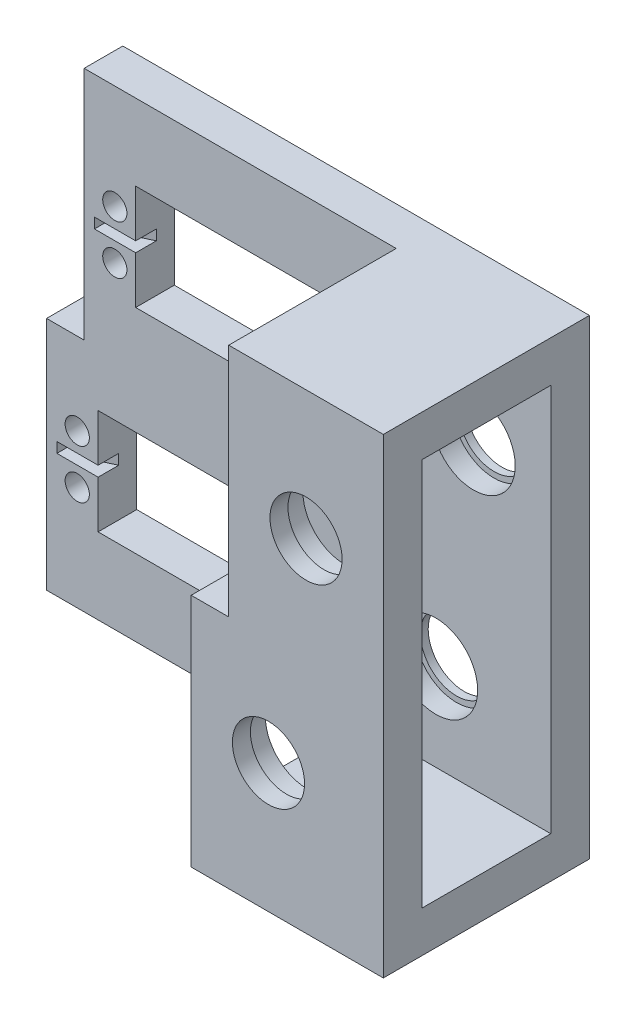
SolidWorks part; units mm, degrees
note: '?' marks a value the reader was unsure of.
ref_plane "Front Plane" through (0, 0, 0) normal (0, 0, 1) x (1, 0, 0)
ref_plane "Top Plane" through (0, 0, 0) normal (0, 1, 0) x (1, 0, 0)
ref_plane "Right Plane" through (0, 0, 0) normal (1, 0, 0) x (0, 0, -1)
sketch "Sketch1" plane through (0, 0, 0) normal (0, 0, 1) x (1, 0, 0)
  line L0 (-15, 0) -> (22.2932, 0)
  line L5 (-15, 91.3619) -> (22.2932, 91.3619)
  line L6 (-15, 0) -> (-15, 91.3619)
  line L7 (22.2932, 0) -> (22.2932, 91.3619)
  line L8 (0, 25) -> (7.2932, 66.3619) construction
  line L9 (0, 25) -> (0, 79.2) construction
  circle A1 centre (0, 25) radius 8.1
  circle A2 centre (7.2932, 66.3619) radius 8.1
  point P4 (0, 0)
  dimension "D2" = 16.2
  dimension "D5" = 25
  dimension "D4" = 15
  dimension "D6" = 25
  dimension "D8" = 42
  dimension "D9" = 10
  dimension "D10" = 15
extrude "Boss-Extrude1" add sketch "Sketch1" along normal blind 40
ref_plane "INNER WALL" through (0, 0, 39) normal (0, 0, 1) x (1, 0, 0)
ref_plane "OUTER WALL" through (0, 0, 32.65) normal (0, 0, 1) x (1, 0, 0)
sketch "Sketch2" plane through (0, 0, 0) normal (0, 1, 0) x (1, 0, 0)
  line L1 (-15, -7.5) -> (22.2932, -7.5)
  line L2 (-15, -7.5) -> (-15, -32.5)
  line L3 (-15, -32.5) -> (22.2932, -32.5)
  line L4 (22.2932, -7.5) -> (22.2932, -32.5)
  line L6 (-15, -40) -> (-15, 0) construction
  line L7 (22.2932, -40) -> (22.2932, 0) construction
  point P9 (22.2932, -20)
  point P10 (22.2932, -20)
  dimension "D1" = 25
extrude "Cut-Extrude1" cut sketch "Sketch2" along normal through all from offset 8
sketch "Sketch10" plane through (0, 0, 40) normal (0, 0, 1) x (1, 0, 0)
  circle A0 centre (7.2932, 66.3619) radius 8.1
  circle A1 centre (0, 25) radius 10.837
  circle A2 centre (7.2932, 66.3619) radius 7
  circle A3 centre (0, 25) radius 7
  circle A4 centre (7.2932, 66.3619) radius 8.1 construction
  circle A5 centre (0, 25) radius 8.1 construction
  dimension "D2" = 14
  dimension "D4" = 14
extrude "Boss-Extrude2" add sketch "Sketch10" against normal offset from surface (3.5 mm away) 4 up to face at (-8.1, 25, 32.5)
sketch "Sketch11" plane through (0, 0, 0) normal (0, 0, -1) x (-1, 0, 0)
  circle A0 centre (-7.2932, 66.3619) radius 8.1
  circle A1 centre (-7.2932, 66.3619) radius 7
  circle A2 centre (0, 25) radius 8.1
  circle A3 centre (0, 25) radius 7
  circle A4 centre (0, 25) radius 8.1 construction
  circle A5 centre (-7.2932, 66.3619) radius 8.1 construction
  dimension "D1" = 14
  dimension "D2" = 14
extrude "Boss-Extrude3" add sketch "Sketch11" against normal offset from surface (3.5 mm away) 4 up to face at (8.1, 25, 7.5)
ref_axis "Axis1" through (0, 25, 3.5) along (0, 0, -1)?
ref_plane "Plane1" through (0, 25, 0) normal (0, -1, 0) x (-1, 0, 0)
ref_axis "Axis2" through (7.2932, 66.3619, 3.5) along (0, 0, -1)?
ref_plane "Plane2" through (0, 66.3619, 0) normal (0, -1, 0) x (-1, 0, 0)
sketch "Sketch12" plane through (0, 0, 0) normal (0, 0, -1) x (-1, 0, 0)
  line L0 (-20.5113, 25) -> (20.5113, 25) construction
  line L1 (15, 0) -> (75.56, 0)
  line L2 (15, 0) -> (15, 91.3619)
  line L3 (15, 91.3619) -> (68.2668, 91.3619)
  line L5 (-20.5113, 66.3619) -> (20.5113, 66.3619) construction
  line L6 (24.66, 35.2) -> (65.56, 35.2)
  line L7 (24.66, 35.2) -> (24.66, 14.8)
  line L8 (24.66, 14.8) -> (65.56, 14.8)
  line L9 (65.56, 35.2) -> (65.56, 14.8)
  line L10 (-22.2932, 91.3619) -> (15, 91.3619) construction
  line L11 (17.3668, 76.5619) -> (58.2668, 76.5619)
  line L12 (17.3668, 76.5619) -> (17.3668, 56.1619)
  line L13 (17.3668, 56.1619) -> (58.2668, 56.1619)
  line L14 (58.2668, 76.5619) -> (58.2668, 56.1619)
  line L16 (15, 0) -> (-22.2932, 0) construction
  line L17 (15, 91.3619) -> (15, 0) construction
  line L18 (68.2668, 91.3619) -> (68.2668, 45.681)
  line L19 (68.2668, 45.681) -> (75.56, 45.681)
  line L20 (75.56, 45.681) -> (75.56, 0)
  line L21 (58.2668, 56.1619) -> (58.2668, 35.2) construction
  line L22 (45.11, 35.2) -> (45.11, 14.8) construction
  line L32 (37.8168, 76.5619) -> (37.8168, 56.1619) construction
  circle A0 centre (35, 25) radius 6.6 construction
  circle A1 centre (0, 25) radius 7 construction
  circle A2 centre (27.7068, 66.3619) radius 6.6 construction
  circle A3 centre (-7.2932, 66.3619) radius 7 construction
  point P15 (45.11, 14.8)
  point P17 (58.2668, 45.681)
  point P27 (17.3668, 66.3619)
  point P34 (37.8168, 56.1619)
  point P53 (45.11, 25)
  dimension "D7" = 13.2
  dimension "D11" = 13.2
  dimension "D2" = 20.4
  dimension "D3" = 40.9
  dimension "D4" = 10.11
  dimension "D9" = 10.11
  dimension "D5" = 35
  dimension "D6" = 10
  dimension "D8" = 10
extrude "Boss-Extrude4" add sketch "Sketch12" against normal up to surface (7.5 mm away) up to face at (8.1, 25, 7.5)
sketch "Sketch13" plane through (0, 0, 0) normal (0, 0, -1) x (-1, 0, 0)
  line L0 (24.66, 35.2) -> (24.66, 14.8) construction
  line L1 (-20.5113, 25) -> (20.5113, 25) construction
  line L2 (65.56, 14.8) -> (65.56, 35.2) construction
  line L3 (17.3668, 76.5619) -> (17.3668, 56.1619) construction
  line L5 (-20.5113, 66.3619) -> (20.5113, 66.3619) construction
  line L6 (58.2668, 56.1619) -> (58.2668, 76.5619) construction
  circle A0 centre (20.61, 29.75) radius 2.3495
  circle A1 centre (20.61, 20.25) radius 2.3495
  circle A2 centre (69.61, 29.75) radius 2.3495
  circle A3 centre (69.61, 20.25) radius 2.3495
  circle A4 centre (13.3168, 71.1119) radius 2.3495
  circle A5 centre (13.3168, 61.6119) radius 2.3495
  circle A6 centre (62.3168, 71.1119) radius 2.3495
  circle A7 centre (62.3168, 61.6119) radius 2.3495
  dimension "D1" = 4.699
  dimension "D2" = 4.05
  dimension "D3" = 9.5
  dimension "D4" = 4.75
  dimension "D5" = 4.05
  dimension "D7" = 9.5
  dimension "D8" = 4.05
  dimension "D9" = 4.75
  dimension "D10" = 4.05
extrude "Cut-Extrude2" cut sketch "Sketch13" against normal up to next
sketch "Sketch22" plane through (0, 0, 7.5) normal (0, 0, 1) x (1, 0, 0)
  line L0 (-58.2668, 56.1619) -> (-58.2668, 76.5619) construction
  line L1 (-58.2668, 65.3619) -> (-66.2668, 65.3619)
  line L2 (-58.2668, 65.3619) -> (-58.2668, 67.3619)
  line L3 (-58.2668, 67.3619) -> (-66.2668, 67.3619)
  line L4 (-66.2668, 65.3619) -> (-66.2668, 67.3619)
  line L5 (-17.3668, 76.5619) -> (-17.3668, 56.1619) construction
  line L6 (-17.3668, 65.3619) -> (-9.3668, 65.3619)
  line L7 (-17.3668, 65.3619) -> (-17.3668, 67.3619)
  line L8 (-17.3668, 67.3619) -> (-9.3668, 67.3619)
  line L9 (-9.3668, 65.3619) -> (-9.3668, 67.3619)
  line L10 (-24.66, 35.2) -> (-24.66, 14.8) construction
  line L11 (-24.66, 24) -> (-16.66, 24)
  line L12 (-24.66, 24) -> (-24.66, 26)
  line L13 (-24.66, 26) -> (-16.66, 26)
  line L14 (-16.66, 24) -> (-16.66, 26)
  line L15 (-65.56, 14.8) -> (-65.56, 35.2) construction
  line L16 (-65.56, 24) -> (-73.56, 24)
  line L17 (-65.56, 24) -> (-65.56, 26)
  line L18 (-65.56, 26) -> (-73.56, 26)
  line L19 (-73.56, 24) -> (-73.56, 26)
  point P24 (-58.2668, 66.3619)
  point P25 (-66.2668, 66.3619)
  point P26 (-73.56, 25)
  point P27 (-65.56, 25)
  dimension "D1" = 2
  dimension "D2" = 8
extrude "Cut-Extrude6" cut sketch "Sketch22" against normal blind 2
sketch "Sketch14" plane through (0, 0, 7.5) normal (0, 0, 1) x (1, 0, 0)
  line L0 (22.2932, 0) -> (22.2932, 91.3619) construction
  line L1 (22.2932, 91.3619) -> (-15, 91.3619)
  line L2 (22.2932, 91.3619) -> (22.2932, 83.3619)
  line L3 (22.2932, 83.3619) -> (-15, 83.3619)
  line L4 (-15, 91.3619) -> (-15, 83.3619)
  line L5 (22.2932, 91.3619) -> (-15, 91.3619) construction
  line L6 (-15, 91.3619) -> (-15, 0) construction
  dimension "D1" = 8
extrude "Boss-Extrude5" add sketch "Sketch14" along normal up to surface (25 mm away) up to face at (-8.1, 25, 32.5)
sketch "Sketch18" plane through (0, 0, 40) normal (0, 0, 1) x (1, 0, 0)
  line L0 (7.2932, 66.3619) -> (7.2932, 25) construction
  line L1 (-15, 91.3619) -> (-7.7068, 91.3619)
  line L2 (-15, 91.3619) -> (-15, 45.681)
  line L3 (-15, 45.681) -> (-7.7068, 45.681)
  line L4 (-7.7068, 91.3619) -> (-7.7068, 45.681)
  line L5 (0, 25) -> (7.2932, 25) construction
  circle A0 centre (7.2932, 66.3619) radius 8.1 construction
  point P13 (7.2932, 45.681)
  dimension "D1" = 15
extrude "Cut-Extrude4" cut sketch "Sketch18" against normal up to surface (32.5 mm away) up to face at (-45.11, 25, 7.5)
sketch "Sketch15" plane through (0, 0, 0) normal (0, 0, -1) x (-1, 0, 0)
  circle A0 centre (0, 25) radius 11
  circle A1 centre (-7.2932, 66.3619) radius 11
  dimension "D1" = 22
extrude "Cut-Extrude3" cut sketch "Sketch15" against normal blind 2
sketch "Sketch19" plane through (0, 0, 32.65) normal (0, 0, 1) x (1, 0, 0)
  line L1 (22.2932, 91.3619) -> (7.2932, 91.3619)
  line L2 (22.2932, 91.3619) -> (22.2932, 116.3619)
  line L3 (22.2932, 116.3619) -> (7.2932, 116.3619)
  line L4 (7.2932, 91.3619) -> (7.2932, 116.3619)
  line L5 (22.2932, 0) -> (7.2932, 0)
  line L6 (22.2932, 0) -> (22.2932, -25)
  line L7 (22.2932, -25) -> (7.2932, -25)
  line L8 (7.2932, 0) -> (7.2932, -25)
  line L9 (-15, 0) -> (22.2932, 0) construction
  dimension "D1" = 15
  dimension "D2" = 25
extrude "Boss-Extrude6" [suppressed] add sketch "Sketch19" against normal blind 10
sketch "Sketch20" plane through (0, 0, 32.65) normal (0, 0, 1) x (1, 0, 0)
  line L0 (-15, 45.681) -> (-7.7068, 45.681) construction
  line L1 (-100.56, 38.181) -> (-68.2668, 38.181)
  line L2 (-100.56, 38.181) -> (-100.56, 53.181)
  line L3 (-100.56, 53.181) -> (-68.2668, 53.181)
  line L4 (-68.2668, 38.181) -> (-68.2668, 53.181)
  line L5 (-75.56, 0) -> (-75.56, 45.681) construction
  line L6 (-68.2668, 45.681) -> (-68.2668, 91.3619) construction
  point P4 (-68.2668, 45.681)
  dimension "D1" = 25
  dimension "D2" = 15
extrude "Boss-Extrude7" [suppressed] add sketch "Sketch20" against normal blind 10 separate body
sketch "Sketch21" [suppressed] plane through (0, 0, 22.65) normal (0, 0, -1) x (-1, 0, 0)
  line L0 (100.56, 38.181) -> (68.2668, 38.181) construction
  line L1 (68.2668, 53.181) -> (75.56, 53.181)
  line L2 (68.2668, 53.181) -> (68.2668, 38.181)
  line L3 (68.2668, 38.181) -> (75.56, 38.181)
  line L4 (75.56, 53.181) -> (75.56, 38.181)
  line L5 (75.56, 0) -> (75.56, 45.681) construction
extrude "Boss-Extrude8" [suppressed] add sketch "Sketch21" along normal up to surface (22.65 mm away)
chamfer "Chamfer2" distance 2 angle 65 4 edges at (-65.56, 25, 5.5) (-58.2668, 66.3619, 5.5) (-17.3668, 66.3619, 5.5) (-24.66, 25, 5.5) first distance on face at (-65.56, 25, 5.125) first distance on face at (-58.2668, 66.3619, 5.125) first distance on face at (-17.3668, 66.3619, 5.125) first distance on face at (-24.66, 25, 5.125)
fillet "Fillet1" [suppressed] radius 7.5
chamfer "Chamfer1" [suppressed] distance 25 angle 45
hole_wizard "M4 Clearance Hole1" [suppressed] positions "Sketch23" profile "Sketch24" hole size "M4" standard "ANSI Metric"
sketch "Sketch23" [suppressed] plane through (0, 0, 22.65) normal (0, 0, -1) x (-1, 0, 0)
  point P0 (-14.7932, 108.8619)
  point P3 (93.06, 45.681)
  point P6 (-14.7932, -17.5)
sketch "Sketch24" plane through (14.7932, 108.8619, 22.65) normal (1, 0, 0) x (0, 1, 0)
  line L0 (0, 0) -> (0, 17.35)
  line L1 (0, 17.35) -> (2.25, 17.35)
  line L2 (2.25, 17.35) -> (2.25, 0.025)
  line L3 (2.25, 0.025) -> (2.275, 0)
  line L5 (2.275, 0) -> (0, 0)
  line L6 (-2.25, 0.025) -> (-2.275, 0) construction
  line L11 (0, -6.35) -> (0, 107.95) construction
  dimension "Thru Hole Dia." = 4.5
  dimension "Thru Hole Depth" = 17.35
  dimension "Near C'Sink Dia." = 4.55
  dimension "Near C'Sink Angle" = 90
fillet "Fillet3" [suppressed] radius 3.5
equation "\"D4@Sketch13\"=\"D3@Sketch13\"/2"
equation "\"D5@Sketch12\"=\"D1@Sketch12\""
equation "\"D8@Sketch13\"=\"D2@Sketch13\""
equation "\"D9@Sketch13\"=\"D7@Sketch13\"/2"
equation "\"D10@Sketch13\"=\"D5@Sketch13\""
